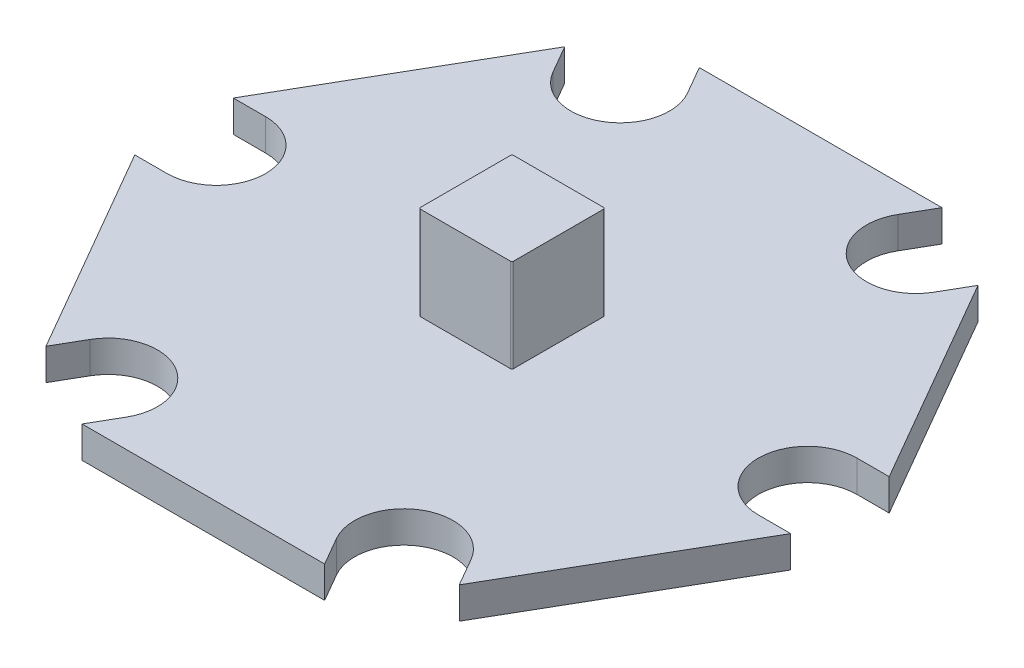
SolidWorks part; units mm, degrees
ref_plane "Front Plane" through (0, 0, 0) normal (0, 0, 1) x (1, 0, 0)
ref_plane "Top Plane" through (0, 0, 0) normal (0, 1, 0) x (1, 0, 0)
ref_plane "Right Plane" through (0, 0, 0) normal (1, 0, 0) x (0, 0, -1)
sketch "Sketch1" plane through (0, 0, 0) normal (0, 1, 0) x (1, 0, 0)
  line L7 (5.7412, 9.9441) -> (-5.7412, 9.9441)
  line L8 (-5.7412, 9.9441) -> (-11.4825, 0)
  line L9 (-11.4825, 0) -> (-5.7412, -9.9441)
  line L10 (-5.7412, -9.9441) -> (5.7412, -9.9441)
  line L11 (5.7412, -9.9441) -> (11.4825, 0)
  line L12 (11.4825, 0) -> (5.7412, 9.9441)
  circle A1 centre (0, 0) radius 9.9441 construction
extrude "Boss-Extrude1" add sketch "Sketch1" along normal blind 1.016
sketch "Sketch2" plane through (0, 1.016, 0) normal (0, 1, 0) x (1, 0, 0)
  line L6 (9.525, 1.5875) -> (13.1378, 1.5875)
  line L12 (9.525, -1.5875) -> (13.1378, -1.5875)
  line L13 (13.1378, 1.5875) -> (13.1378, -1.5875)
  arc A1 (9.525, 1.5875) -> (9.525, -1.5875) centre (9.525, 0) ccw
  dimension "D1" = 9.525
extrude "Cut-Extrude1" cut sketch "Sketch2" against normal blind 1.016
ref_axis "Axis1" through (0, 4.2168, 0) along (0, -1, 0)
pattern_circular "CirPattern1" count 6 every 60 about axis through (0, 4.2168, 0) along (0, -1, 0) of "Cut-Extrude1"
sketch "Sketch3" plane through (0, 1.016, 0) normal (0, 1, 0) x (1, 0, 0)
  line L1 (-1.5, -1.5) -> (-1.5, 1.5)
  line L2 (-1.5, -1.5) -> (1.5, -1.5)
  line L3 (-1.5, 1.5) -> (1.5, 1.5)
  line L4 (1.5, -1.5) -> (1.5, 1.5)
  line L6 (-1.5, 1.5) -> (-0.0012, 0.0012) construction
  point P9 (0, 0)
  dimension "D1" = 3
  dimension "D2" = 3
extrude "Boss-Extrude2" add sketch "Sketch3" along normal blind 3
fillet "Fillet1" radius 0.0508 1 edges at (1.5, 2.516, 1.5)
fillet "Fillet2" radius 0.0508 1 edges at (-1.5, 2.516, -1.5)
fillet "Fillet3" radius 0.0508 1 edges at (1.5, 2.516, -1.5)
fillet "Fillet4" radius 0.0508 1 edges at (-1.5, 2.516, 1.5)
